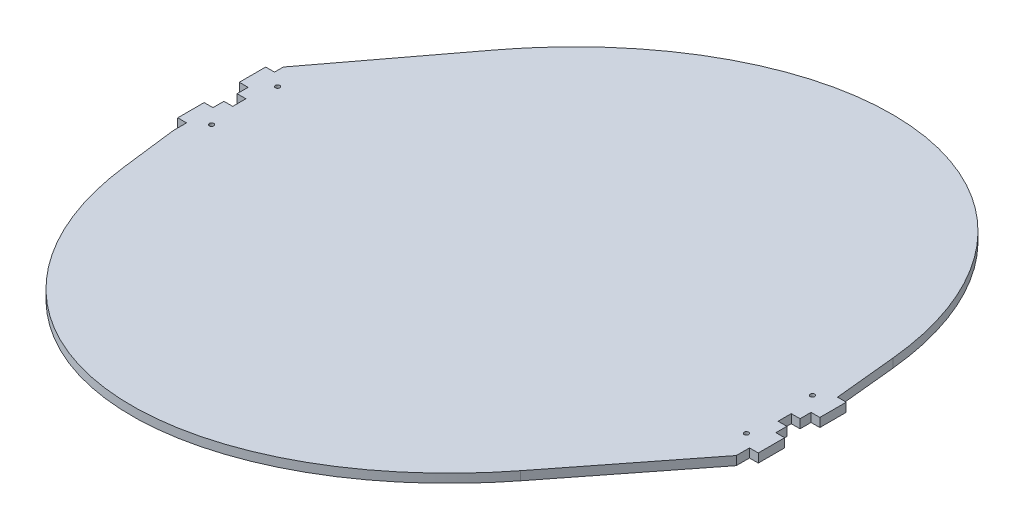
SolidWorks part; units mm, degrees
ref_plane "Front Plane" through (0, 0, 0) normal (0, 0, 1) x (1, 0, 0)
ref_plane "Top Plane" through (0, 0, 0) normal (0, 1, 0) x (1, 0, 0)
ref_plane "Right Plane" through (0, 0, 0) normal (1, 0, 0) x (0, 0, -1)
sketch "Sketch1" plane through (0, 0, 0) normal (0, 1, 0) x (1, 0, 0)
  line L0 (-320, -65) -> (-312.1702, -128.3352)
  line L1 (-217.5479, 195.7385) -> (-320, 60)
  line L2 (-320, 60) -> (-320, 50)
  line L3 (-320, 50) -> (-330, 50)
  line L4 (-330, 50) -> (-330, 20)
  line L5 (-330, 20) -> (-320, 20)
  line L6 (-320, 20) -> (-320, -20)
  line L7 (-320, -20) -> (-330, -20)
  line L8 (-330, -20) -> (-330, -50)
  line L9 (-330, -50) -> (-320, -50)
  line L10 (-320, -50) -> (-320, -65)
  line L11 (212.2821, -202.5885) -> (320, -65)
  line L12 (320, -50) -> (320, -65)
  line L13 (320, -50) -> (330, -50)
  line L14 (330, -50) -> (330, -20)
  line L15 (330, -20) -> (320, -20)
  line L16 (320, -20) -> (320, 20)
  line L17 (320, 20) -> (330, 20)
  line L18 (330, 20) -> (330, 50)
  line L19 (330, 50) -> (320, 50)
  line L20 (320, 50) -> (320, 51)
  line L21 (320, 51) -> (313.0913, 120.0927)
  ellipse E0 centre (0, 0) end of major axis (-190, -329.0897) minor radius 290 (313.0913, 120.0927) -> (-217.5479, 195.7385) ccw
  ellipse E1 centre (0, 0) end of major axis (-190, -329.0897) minor radius 290 (-312.1702, -128.3352) -> (212.2821, -202.5885) ccw
extrude "Boss-Extrude1" add sketch "Sketch1" along normal blind 10
sketch "Sketch2" plane through (0, 0, 0) normal (0, -1, 0) x (1, 0, 0)
  line L0 (0, 0) -> (595.7693, 0) construction
  line L1 (320, 20) -> (320, -20) construction
  line L2 (320, -7.5) -> (310, -7.5)
  line L3 (320, -7.5) -> (320, 7.5)
  line L4 (320, 7.5) -> (310, 7.5)
  line L5 (310, -7.5) -> (310, 7.5)
  line L6 (0, 0) -> (0, 484.7158) construction
  line L7 (-310, -7.5) -> (-310, 7.5)
  line L8 (-320, 7.5) -> (-310, 7.5)
  line L9 (-320, -7.5) -> (-320, 7.5)
  line L10 (-320, -7.5) -> (-310, -7.5)
  point P3 (-320, 0)
  point P10 (310, 0)
  point P11 (320, 0)
  point P13 (-310, 0)
  dimension "D1" = 15
  dimension "D2" = 10
extrude "Cut-Extrude1" cut sketch "Sketch2" against normal blind 10
hole_wizard "Ø5.0 (5) Diameter Hole2" positions "Sketch5" profile "Sketch6" hole size "Ø5.0" standard "ANSI Metric"
sketch "Sketch5" plane through (0, -10, 0) normal (0, -1, 0) x (-1, 0, 0)
  point P0 (304, 37.5)
  point P3 (304, -37.5)
  point P6 (-304, -37.5)
  point P9 (-304, 37.5)
sketch "Sketch6" plane through (-304, -10, -37.5) normal (1, 0, 0) x (0, 0, -1)
  line L0 (0, 0) -> (0, 26.5022)
  line L1 (0, 26.5022) -> (2.5, 25)
  line L2 (2.5, 25) -> (2.5, 0)
  line L3 (2.5, 0) -> (0, 0)
  line L4 (0, 26.5022) -> (-2.5, 25) construction
  line L5 (0, -6.35) -> (0, 107.95) construction
  dimension "Hole Dia." = 5
  dimension "Hole Depth" = 25
  dimension "Drill Angle" = 118
